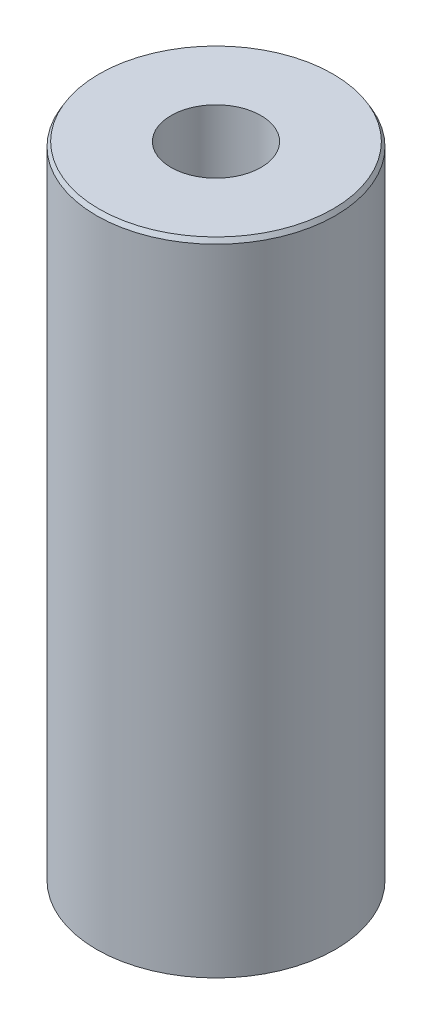
SolidWorks part; units mm, degrees
ref_plane "Front Plane" through (0, 0, 0) normal (0, 0, 1) x (1, 0, 0)
ref_plane "Top Plane" through (0, 0, 0) normal (0, 1, 0) x (1, 0, 0)
ref_plane "Right Plane" through (0, 0, 0) normal (1, 0, 0) x (0, 0, -1)
sketch "Sketch1" plane through (0, 0, 0) normal (0, 1, 0) x (1, 0, 0)
  circle A0 centre (0, 0) radius 47.5
  dimension "SHAFT_OD" = 95
extrude "Boss-Extrude1" add sketch "Sketch1" along normal blind 255.3626
sketch "Sketch2" plane through (0, 0, 0) normal (0, 1, 0) x (1, 0, 0)
  circle A0 centre (0, 0) radius 17.8825
  dimension "BORE_D" = 35.765
extrude "Cut-Extrude1" cut sketch "Sketch2" along normal through all
chamfer "Chamfer1" distance 1.7699 angle 29.836 2 edges at (0, 255.3626, 47.5) (0, 0, 47.5) first distance on face at (0, 255.3626, 47.5) first distance on face at (0, 0, 17.8825)
